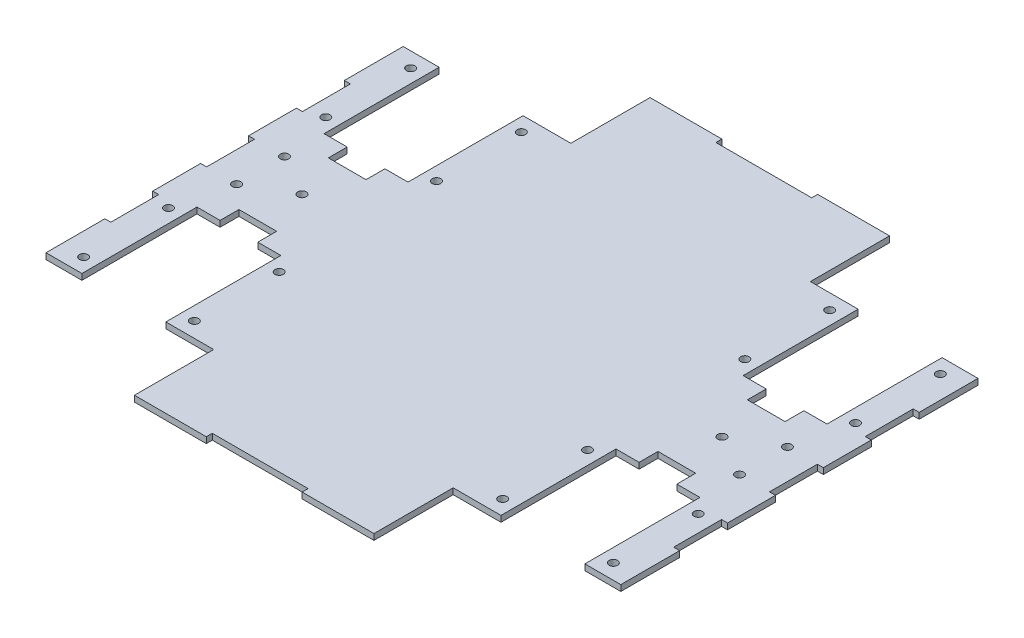
SolidWorks part; units mm, degrees
ref_plane "Front Plane" through (0, 0, 0) normal (0, 0, 1) x (1, 0, 0)
ref_plane "Top Plane" through (0, 0, 0) normal (0, 1, 0) x (1, 0, 0)
ref_plane "Right Plane" through (0, 0, 0) normal (1, 0, 0) x (0, 0, -1)
sketch "Sketch1" plane through (0, 0, 0) normal (0, 1, 0) x (1, 0, 0)
  line L0 (152.4, 94.7) -> (63.5, 94.7)
  line L1 (-152.4, -136.7) -> (152.4, -136.7)
  line L2 (-152.4, -136.7) -> (-152.4, 136.7)
  line L3 (-152.4, 136.7) -> (152.4, 136.7)
  line L4 (152.4, -136.7) -> (152.4, 136.7)
  line L5 (-152.4, -136.7) -> (152.4, 136.7) construction
  line L6 (-152.4, 136.7) -> (152.4, -136.7) construction
  line L7 (63.5, 94.7) -> (63.5, 136.7)
  line L8 (-152.4, 94.7) -> (-63.5, 94.7)
  line L9 (-63.5, 94.7) -> (-63.5, 136.7)
  line L10 (-152.4, -94.7) -> (-63.5, -94.7)
  line L11 (-63.5, -94.7) -> (-63.5, -136.7)
  line L12 (152.4, -94.7) -> (63.5, -94.7)
  line L13 (63.5, -94.7) -> (63.5, -136.7)
  line L14 (-88.8476, 33.7) -> (88.8476, 33.7) construction
  line L15 (88.8476, 33.7) -> (133.35, 33.7)
  line L16 (88.8476, 33.7) -> (88.8476, 94.7)
  line L17 (88.8476, 94.7) -> (133.35, 94.7)
  line L18 (133.35, 33.7) -> (133.35, 94.7)
  line L19 (88.8476, 33.7) -> (133.35, 94.7) construction
  line L20 (88.8476, 94.7) -> (133.35, 33.7) construction
  line L21 (88.8476, -33.7) -> (133.35, -33.7)
  line L22 (88.8476, -33.7) -> (88.8476, -94.7)
  line L23 (88.8476, -94.7) -> (133.35, -94.7)
  line L24 (133.35, -33.7) -> (133.35, -94.7)
  line L25 (88.8476, -33.7) -> (133.35, -94.7) construction
  line L26 (88.8476, -94.7) -> (133.35, -33.7) construction
  line L27 (-133.35, -33.7) -> (-88.8476, -33.7)
  line L28 (-133.35, -33.7) -> (-133.35, -94.7)
  line L29 (-133.35, -94.7) -> (-88.8476, -94.7)
  line L30 (-88.8476, -33.7) -> (-88.8476, -94.7)
  line L31 (-133.35, -33.7) -> (-88.8476, -94.7) construction
  line L32 (-133.35, -94.7) -> (-88.8476, -33.7) construction
  line L33 (-133.35, 33.7) -> (-88.8476, 33.7)
  line L34 (-133.35, 33.7) -> (-133.35, 94.7)
  line L35 (-133.35, 94.7) -> (-88.8476, 94.7)
  line L36 (-88.8476, 33.7) -> (-88.8476, 94.7)
  line L37 (-133.35, 33.7) -> (-88.8476, 94.7) construction
  line L38 (-133.35, 94.7) -> (-88.8476, 33.7) construction
  line L39 (-149.225, 38.1) -> (-149.225, 12.7) construction
  line L40 (152.4, 12.7) -> (149.225, 12.7)
  line L41 (152.4, 12.7) -> (152.4, -12.7)
  line L42 (152.4, -12.7) -> (149.225, -12.7)
  line L43 (149.225, 12.7) -> (149.225, -12.7)
  line L44 (152.4, 63.5) -> (149.225, 63.5)
  line L45 (152.4, 63.5) -> (152.4, 38.1)
  line L46 (152.4, 38.1) -> (149.225, 38.1)
  line L47 (149.225, 63.5) -> (149.225, 38.1)
  line L48 (152.4, -38.1) -> (149.225, -38.1)
  line L49 (152.4, -38.1) -> (152.4, -63.5)
  line L50 (152.4, -63.5) -> (149.225, -63.5)
  line L51 (149.225, -38.1) -> (149.225, -63.5)
  line L52 (-149.225, 63.5) -> (-152.4, 63.5)
  line L53 (-149.225, 63.5) -> (-149.225, 38.1)
  line L54 (-149.225, 38.1) -> (-152.4, 38.1)
  line L55 (-152.4, 63.5) -> (-152.4, 38.1)
  line L56 (-149.225, 12.7) -> (-152.4, 12.7)
  line L57 (-149.225, 12.7) -> (-149.225, -12.7)
  line L58 (-149.225, -12.7) -> (-152.4, -12.7)
  line L59 (-152.4, 12.7) -> (-152.4, -12.7)
  line L60 (-149.225, -38.1) -> (-152.4, -38.1)
  line L61 (-149.225, -38.1) -> (-149.225, -63.5)
  line L62 (-149.225, -63.5) -> (-152.4, -63.5)
  line L63 (-152.4, -38.1) -> (-152.4, -63.5)
  line L64 (-149.225, -12.7) -> (-149.225, -38.1) construction
  line L65 (149.225, 38.1) -> (149.225, 12.7) construction
  line L66 (149.225, -12.7) -> (149.225, -38.1) construction
  line L67 (133.35, -12.7) -> (133.35, 12.7) construction
  line L68 (25.4, -136.7) -> (-25.4, -136.7)
  line L69 (25.4, -136.7) -> (25.4, -133.525)
  line L70 (25.4, -133.525) -> (-25.4, -133.525)
  line L71 (-25.4, -136.7) -> (-25.4, -133.525)
  line L72 (25.4, 136.7) -> (-25.4, 136.7)
  line L73 (25.4, 136.7) -> (25.4, 133.525)
  line L74 (25.4, 133.525) -> (-25.4, 133.525)
  line L75 (-25.4, 136.7) -> (-25.4, 133.525)
  line L76 (133.35, -12.7) -> (111.353, 0) construction
  line L77 (111.353, 0) -> (133.35, 12.7) construction
  line L78 (-133.35, -12.7) -> (-133.35, 12.7) construction
  line L79 (81.7565, 41.7) -> (140.4411, 41.7) construction
  line L80 (81.7565, 41.7) -> (81.7565, 86.7) construction
  line L81 (81.7565, 86.7) -> (140.4411, 86.7) construction
  line L82 (140.4411, 41.7) -> (140.4411, 86.7) construction
  line L83 (81.7565, 41.7) -> (140.4411, 86.7) construction
  line L84 (81.7565, 86.7) -> (140.4411, 41.7) construction
  line L85 (81.7565, -86.7) -> (140.4411, -86.7) construction
  line L86 (81.7565, -86.7) -> (81.7565, -41.7) construction
  line L87 (81.7565, -41.7) -> (140.4411, -41.7) construction
  line L88 (140.4411, -86.7) -> (140.4411, -41.7) construction
  line L89 (81.7565, -86.7) -> (140.4411, -41.7) construction
  line L90 (81.7565, -41.7) -> (140.4411, -86.7) construction
  line L91 (-140.4411, -86.7) -> (-81.7565, -86.7) construction
  line L92 (-140.4411, -86.7) -> (-140.4411, -41.7) construction
  line L93 (-140.4411, -41.7) -> (-81.7565, -41.7) construction
  line L94 (-81.7565, -86.7) -> (-81.7565, -41.7) construction
  line L95 (-140.4411, -86.7) -> (-81.7565, -41.7) construction
  line L96 (-140.4411, -41.7) -> (-81.7565, -86.7) construction
  line L97 (-140.4411, 41.7) -> (-81.7565, 41.7) construction
  line L98 (-140.4411, 41.7) -> (-140.4411, 86.7) construction
  line L99 (-140.4411, 86.7) -> (-81.7565, 86.7) construction
  line L100 (-81.7565, 41.7) -> (-81.7565, 86.7) construction
  line L101 (-140.4411, 41.7) -> (-81.7565, 86.7) construction
  line L102 (-140.4411, 86.7) -> (-81.7565, 41.7) construction
  line L103 (-133.35, 12.7) -> (-111.353, 0) construction
  line L104 (-111.353, 0) -> (-133.35, -12.7) construction
  line L106 (-121.0988, 23.7) -> (-101.0988, 23.7)
  line L107 (-121.0988, 23.7) -> (-121.0988, 33.7)
  line L108 (-121.0988, 33.7) -> (-101.0988, 33.7)
  line L109 (-101.0988, 23.7) -> (-101.0988, 33.7)
  line L110 (-121.0988, 23.7) -> (-101.0988, 33.7) construction
  line L111 (-121.0988, 33.7) -> (-101.0988, 23.7) construction
  line L112 (-121.0988, -23.7) -> (-101.0988, -23.7)
  line L113 (-121.0988, -23.7) -> (-121.0988, -33.7)
  line L114 (-121.0988, -33.7) -> (-101.0988, -33.7)
  line L115 (-101.0988, -23.7) -> (-101.0988, -33.7)
  line L116 (-121.0988, -23.7) -> (-101.0988, -33.7) construction
  line L117 (-121.0988, -33.7) -> (-101.0988, -23.7) construction
  line L118 (101.0988, -23.7) -> (121.0988, -23.7)
  line L119 (101.0988, -23.7) -> (101.0988, -33.7)
  line L120 (101.0988, -33.7) -> (121.0988, -33.7)
  line L121 (121.0988, -23.7) -> (121.0988, -33.7)
  line L122 (101.0988, -23.7) -> (121.0988, -33.7) construction
  line L123 (101.0988, -33.7) -> (121.0988, -23.7) construction
  line L124 (101.0988, 23.7) -> (121.0988, 23.7)
  line L125 (101.0988, 23.7) -> (101.0988, 33.7)
  line L126 (101.0988, 33.7) -> (121.0988, 33.7)
  line L127 (121.0988, 23.7) -> (121.0988, 33.7)
  line L128 (101.0988, 23.7) -> (121.0988, 33.7) construction
  line L129 (101.0988, 33.7) -> (121.0988, 23.7) construction
  circle A0 centre (133.35, -12.7) radius 2.25
  circle A1 centre (133.35, 12.7) radius 2.25
  circle A2 centre (111.353, 0) radius 2.25
  circle A3 centre (-81.7565, 41.7) radius 2.25
  circle A4 centre (-81.7565, 86.7) radius 2.25
  circle A5 centre (-140.4411, 86.7) radius 2.25
  circle A6 centre (-140.4411, 41.7) radius 2.25
  circle A7 centre (-81.7565, -41.7) radius 2.25
  circle A8 centre (-81.7565, -86.7) radius 2.25
  circle A9 centre (-140.4411, -86.7) radius 2.25
  circle A10 centre (-140.4411, -41.7) radius 2.25
  circle A11 centre (81.7565, -41.7) radius 2.25
  circle A12 centre (81.7565, -86.7) radius 2.25
  circle A13 centre (140.4411, -41.7) radius 2.25
  circle A14 centre (140.4411, -86.7) radius 2.25
  circle A15 centre (81.7565, 41.7) radius 2.25
  circle A16 centre (81.7565, 86.7) radius 2.25
  circle A17 centre (140.4411, 86.7) radius 2.25
  circle A18 centre (140.4411, 41.7) radius 2.25
  circle A19 centre (-133.35, -12.7) radius 2.25
  circle A20 centre (-133.35, 12.7) radius 2.25
  circle A21 centre (-111.353, 0) radius 2.25
  point P0 (0, 0)
  point P18 (111.0988, 64.2)
  point P23 (111.0988, -64.2)
  point P28 (-111.0988, -64.2)
  point P33 (-111.0988, 64.2)
  point P38 (0, 33.7)
  point P43 (149.225, 0)
  point P68 (0, -133.525)
  point P79 (111.0988, 64.2)
  point P80 (133.35, 0)
  point P85 (111.0988, -64.2)
  point P90 (-111.0988, -64.2)
  point P95 (-111.0988, 64.2)
  point P122 (-111.0988, 28.7)
  point P123 (-133.35, 0)
  point P128 (-111.0988, -28.7)
  point P133 (111.0988, -28.7)
  point P138 (111.0988, 28.7)
  dimension "D12" = 4.5
  dimension "D14" = 45
  dimension "D16" = 4.5
  dimension "D1" = 304.8
  dimension "D2" = 273.4
  dimension "D3" = 42
  dimension "D4" = 88.9
  dimension "D5" = 61
  dimension "D6" = 44.5024
  dimension "D7" = 19.05
  dimension "D8" = 25.4
  dimension "D9" = 3.175
  dimension "D10" = 50.8
  dimension "D11" = 3.175
  dimension "D13" = 25.4
  dimension "D15" = 58.6846
  dimension "D17" = 10
  dimension "D18" = 20
extrude "Boss-Extrude1" add sketch "Sketch1" along normal blind 3.175 contours L13 L12 L4 L0 L7 L3 L9 L8 L2 L10 L11 L1 region at (0, 0, 0)
